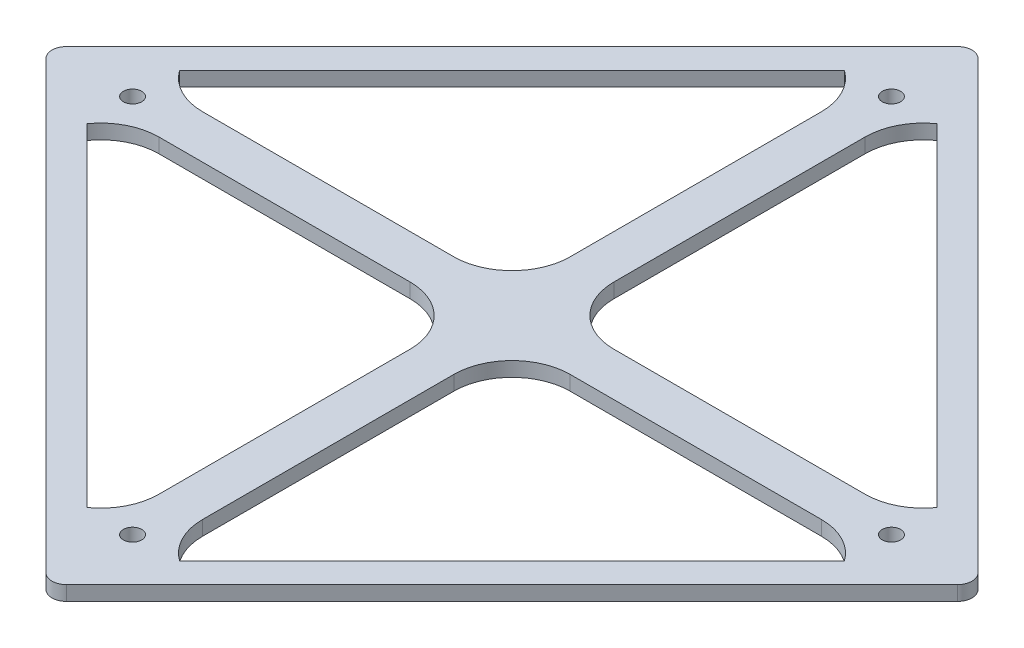
SolidWorks part; units mm, degrees
ref_plane "Front Plane" through (0, 0, 0) normal (0, 0, 1) x (1, 0, 0)
ref_plane "Top Plane" through (0, 0, 0) normal (0, 1, 0) x (1, 0, 0)
ref_plane "Right Plane" through (0, 0, 0) normal (1, 0, 0) x (0, 0, -1)
sketch "Sketch1" plane through (0, 0, 0) normal (0, 1, 0) x (1, 0, 0)
  line L0 (0, -101.6) -> (-101.6, 0)
  line L1 (-101.6, 0) -> (0, 101.6)
  line L2 (0, 101.6) -> (101.6, 0)
  line L3 (101.6, 0) -> (0, -101.6)
  line L4 (0, -101.6) -> (0, 101.6) construction
  line L5 (-101.6, 0) -> (101.6, 0) construction
  line L6 (0, -82.7315) -> (-82.7315, 0) construction
  line L7 (-82.7315, 0) -> (0, 82.7315) construction
  line L8 (0, 82.7315) -> (82.7315, 0) construction
  line L9 (82.7315, 0) -> (0, -82.7315) construction
  circle A0 centre (0, 82.7315) radius 2
  circle A1 centre (-82.7315, 0) radius 2
  circle A2 centre (0, -82.7315) radius 2
  circle A3 centre (82.7315, 0) radius 2
  point P12 (0, 0)
  dimension "D3" = 4
  dimension "D1" = 203.2
  dimension "D2" = 117
extrude "Boss-Extrude1" add sketch "Sketch1" along normal blind 3.175
sketch "Sketch2" plane through (0, 3.175, 0) normal (0, 1, 0) x (1, 0, 0)
  line L0 (82.55, -10.0697) -> (82.55, -4.7625)
  line L1 (82.55, 10.0697) -> (10.0697, 82.55)
  line L2 (10.0697, 82.55) -> (4.7625, 82.55)
  line L3 (-10.0697, 82.55) -> (-82.55, 10.0697)
  line L4 (-82.55, 10.0697) -> (-82.55, 4.7625)
  line L5 (-82.55, -10.0697) -> (-10.0697, -82.55)
  line L6 (-10.0697, -82.55) -> (-4.7625, -82.55)
  line L7 (10.0697, -82.55) -> (82.55, -10.0697)
  line L8 (101.6, 0) -> (0, 101.6) construction
  line L9 (-46.3099, -46.3099) -> (46.3099, 46.3099) construction
  line L10 (-101.6, 0) -> (0, -101.6) construction
  line L11 (82.55, 4.7625) -> (82.55, 10.0697)
  line L12 (101.6, 0) -> (-101.6, 0) construction
  line L13 (0, -101.6) -> (0, 101.6) construction
  line L14 (-4.7625, -82.55) -> (-4.7625, -4.7625)
  line L15 (4.7625, 82.55) -> (4.7625, 4.7625)
  line L16 (4.7625, 4.7625) -> (82.55, 4.7625)
  line L17 (82.55, -4.7625) -> (4.7625, -4.7625)
  line L18 (4.7625, -4.7625) -> (4.7625, -82.55)
  line L19 (-4.7625, -4.7625) -> (-82.55, -4.7625)
  line L20 (-82.55, 4.7625) -> (-4.7625, 4.7625)
  line L21 (-4.7625, 4.7625) -> (-4.7625, 82.55)
  line L22 (4.7625, -82.55) -> (10.0697, -82.55)
  line L23 (-82.55, -4.7625) -> (-82.55, -10.0697)
  line L24 (-4.7625, 82.55) -> (-10.0697, 82.55)
  line L25 (0, -101.6) -> (101.6, 0) construction
  dimension "D1" = 6.35
  dimension "D2" = 19.05
  dimension "D3" = 9.525
extrude "Cut-Extrude1" cut sketch "Sketch2" against normal through all contours L19 L23 L5 L6 L14 | L21 L24 L3 L4 L20 | L15 L16 L11 L1 L2 | L18 L22 L7 L0 L17 region at (32.3541, 3.175, -32.3541) region at (-32.3541, 3.175, -32.3541) region at (-32.3541, 3.175, 32.3541)
fillet "Fillet1" radius 12.7 12 edges at (4.7625, 1.5875, 82.55) (4.7625, 1.5875, 4.7625) (82.55, 1.5875, 4.7625) (-4.7625, 1.5875, 82.55) (-82.55, 1.5875, 4.7625) (-82.55, 1.5875, -4.7625) (-4.7625, 1.5875, -82.55) (4.7625, 1.5875, -82.55) (82.55, 1.5875, -4.7625) (4.7625, 1.5875, -4.7625) (-4.7625, 1.5875, -4.7625) (-4.7625, 1.5875, 4.7625)
fillet "Fillet2" radius 3.175 4 edges at (101.6, 1.5875, 0) (0, 1.5875, -101.6) (-101.6, 1.5875, 0) (0, 1.5875, 101.6)
